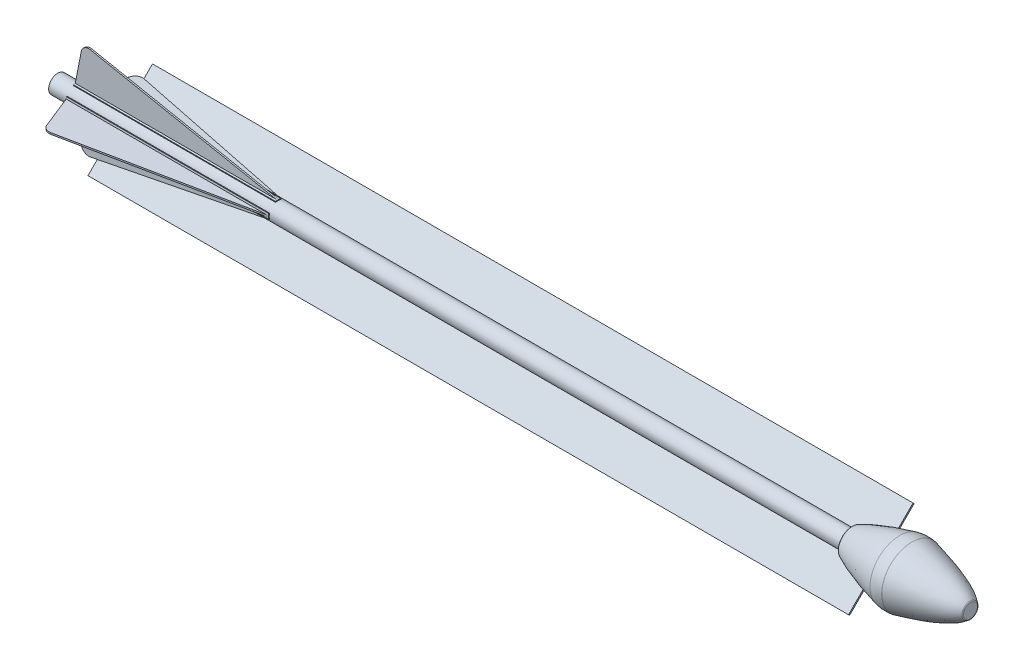
SolidWorks part; units mm, degrees
ref_plane "正面" through (0, 0, 0) normal (0, 0, 1) x (1, 0, 0)
ref_plane "平面" through (0, 0, 0) normal (0, 1, 0) x (1, 0, 0)
ref_plane "右側面" through (0, 0, 0) normal (1, 0, 0) x (0, 0, -1)
sketch "ｽｹｯﾁ1" plane through (0, 0, 0) normal (0, 0, 1) x (1, 0, 0)
  line L0 (-30.4177, 20.3227) -> (-30.4177, -19.1312)
  line L1 (-69.8771, 9.5958) -> (-69.8771, -8.4042)
  line L5 (8.174, 5.5958) -> (8.174, -4.4042)
  line L6 (-38.4177, 20.0342) -> (-38.4177, -18.8426)
  line L7 (10.8234, 0.5958) -> (-591.826, 0.5958)
  line L8 (-591.826, 6.5958) -> (-74.6461, 6.5958)
  line L9 (-591.826, 6.5958) -> (-591.826, -5.4042)
  line L10 (-591.826, -5.4042) -> (-74.6461, -5.4042)
  line L11 (-74.6461, 6.5958) -> (-74.6461, -5.4042)
  line L12 (-591.826, 6.5958) -> (-74.6461, -5.4042) construction
  line L13 (-591.826, -5.4042) -> (-74.6461, 6.5958) construction
  line L14 (-74.6461, -4.4042) -> (-591.826, -4.4042)
  line L15 (-74.6461, -4.4042) -> (-74.6461, 5.5958)
  line L16 (-74.6461, 5.5958) -> (-591.826, 5.5958)
  line L17 (-591.826, -4.4042) -> (-591.826, 5.5958)
  line L18 (-74.6461, -4.4042) -> (-591.826, 5.5958) construction
  line L19 (-74.6461, 5.5958) -> (-591.826, -4.4042) construction
  line L20 (-74.6461, 6.5958) -> (-56.932, 6.5958)
  line L21 (-74.6461, 6.5958) -> (-74.6461, -5.4042)
  line L22 (-74.6461, -5.4042) -> (-56.932, -5.4042)
  line L23 (-56.932, 6.5958) -> (-56.932, -5.4042)
  line L24 (-74.6461, 6.5958) -> (-56.932, -5.4042) construction
  line L25 (-74.6461, -5.4042) -> (-56.932, 6.5958) construction
  line L26 (-74.6461, 5.5958) -> (-56.932, 5.5958)
  line L27 (-74.6461, 5.5958) -> (-74.6461, -4.4042)
  line L28 (-74.6461, -4.4042) -> (-56.932, -4.4042)
  line L29 (-56.932, 5.5958) -> (-56.932, -4.4042)
  line L30 (-74.6461, 5.5958) -> (-56.932, -4.4042) construction
  line L31 (-74.6461, -4.4042) -> (-56.932, 5.5958) construction
  circle A0 centre (-33.7114, 0.5958) radius 20
  parabola Q1 (-38.4177, -18.8426) -> (-38.4177, 20.0342) focus (-76.1023, 0.5958) apex (-78.4613, 0.5958)
  parabola Q2 (-30.4177, -19.1312) -> (-30.4177, 20.3227) focus (8.4644, 0.5958) apex (10.8234, 0.5958)
  point P5 (-333.236, 0.5958)
  point P22 (-591.826, 0.5958)
  point P23 (-333.236, 0.5958)
  point P30 (-65.7891, 0.5958)
  point P33 (-65.7891, 0.5958)
  dimension "D1" = 40
  dimension "D18" = 40
  dimension "D7" = 20
  dimension "D9" = 0
  dimension "D10" = 0
  dimension "D11" = 20
  dimension "D13" = 20
  dimension "D15" = 20
  dimension "D2" = 18
  dimension "D5" = 10
  dimension "D8" = 2.359
  dimension "D19" = 78.0511
  dimension "D3" = 2.359
  dimension "D17" = 12
  dimension "D21" = 600
  dimension "D22" = 10
revolve "回転2" add sketch "ｽｹｯﾁ1" angle 360 about L7 region at (-23.4152, 8.6926, 0) region at (-34.4081, 10.5229, 0) region at (-44.7941, 8.4849, 0) region at (-57.1653, 10.2678, 0) region at (-6.3628, 7.5549, 0) region at (-63.4046, 6.0958, 0) region at (-72.2616, 6.0958, 0) region at (-333.5362, 6.0959, 0) region at (-75.0407, 5.934, 0)
fillet "ﾌｨﾚｯﾄ2" radius 1 2 edges at (-69.8771, 9.5958, 0) (8.174, 5.5958, 0)
sketch "ｽｹｯﾁ5" plane through (-591.826, 0, 0) normal (-1, 0, 0) x (0, 0, 1)
  circle A0 centre (0, 0.5958) radius 6.5
  circle A1 centre (0, 0.5958) radius 7.57
  dimension "D1" = 13
extrude "ﾎﾞｽ - 押し出し2" add sketch "ｽｹｯﾁ5" along normal blind 2 separate body
sketch "ｽｹｯﾁ6" plane through (0, 0, 0) normal (0, 0, 1) x (1, 0, 0)
  line L0 (-591.826, 6.5958) -> (-591.826, -5.4042) construction
  line L1 (-579.826, 2.2958) -> (-446.826, 2.2958)
  line L2 (-579.826, 2.2958) -> (-579.826, -1.1042)
  line L3 (-579.826, -1.1042) -> (-446.826, -1.1042)
  line L4 (-446.826, 2.2958) -> (-446.826, -1.1042)
  line L5 (-579.826, 2.2958) -> (-446.826, -1.1042) construction
  line L6 (-579.826, -1.1042) -> (-446.826, 2.2958) construction
  line L7 (-591.826, -5.4042) -> (-69.8771, -5.4042) construction
  point P4 (-513.326, 0.5958)
  point P7 (-579.826, 0.5958)
  dimension "D1" = 12
  dimension "D2" = 133
  dimension "D3" = 3.4
  dimension "D4" = 6
extrude "ﾎﾞｽ - 押し出し3" add sketch "ｽｹｯﾁ6" along normal up to surface and the other way up to surface up to face at (-593.826, -5.9042, 0) other way up to face at (-593.826, -5.9042, 0)
sketch "ｽｹｯﾁ7" plane through (0, 0, 0) normal (0, 1, 0) x (1, 0, 0)
  line L0 (-591.826, 6) -> (-591.826, -6) construction
  line L1 (-579.826, 1.7) -> (-446.826, 1.7)
  line L2 (-579.826, 1.7) -> (-579.826, -1.7)
  line L3 (-579.826, -1.7) -> (-446.826, -1.7)
  line L4 (-446.826, 1.7) -> (-446.826, -1.7)
  line L5 (-579.826, 1.7) -> (-446.826, -1.7) construction
  line L6 (-579.826, -1.7) -> (-446.826, 1.7) construction
  line L7 (-591.826, -6) -> (-579.826, -6) construction
  point P4 (-513.326, 0)
  point P7 (-579.826, 0)
  dimension "D1" = 3.4
  dimension "D2" = 133
  dimension "D3" = 12
  dimension "D4" = 6
extrude "ﾎﾞｽ - 押し出し4" add sketch "ｽｹｯﾁ7" along normal up to surface and the other way up to surface up to face at (-593.826, -5.9042, 0) other way up to face at (-593.826, -5.9042, 0)
sketch "ｽｹｯﾁ8" plane through (-593.826, 0, 0) normal (-1, 0, 0) x (0, 0, 1)
  circle A0 centre (0, 0.5958) radius 8.0163
  circle A1 centre (0, 0.5958) radius 5
  circle A2 centre (0, 0.5958) radius 6.5
  circle M3 centre (0, 0.5958) radius 7.57
  circle M4 centre (0, 0.5958) radius 6.5
extrude "ｶｯﾄ - 押し出し1" cut sketch "ｽｹｯﾁ8" against normal blind 182 and the other way blind 2 contours M3 M4 | A1 region at (-593.826, 0.5958, 0) region at (-593.826, 0.5958, -7.3558)
sketch "ｽｹｯﾁ9" plane through (-591.826, 0, 0) normal (-1, 0, 0) x (0, 0, 1)
  line L5 (0, 0.5958) -> (7, 0.5958)
  line L6 (0, 0.5958) -> (0, -6.4042)
  line L7 (0, -6.4042) -> (7, -6.4042)
  line L8 (7, 0.5958) -> (7, -6.4042)
  line L9 (0, 0.5958) -> (7, -6.4042) construction
  line L10 (0, -6.4042) -> (7, 0.5958) construction
  line L11 (0, 0.5958) -> (10, 0.5958)
  line L12 (0, 0.5958) -> (0, -9.4042)
  line L13 (0, -9.4042) -> (10, -9.4042)
  line L14 (10, 0.5958) -> (10, -9.4042)
  line L15 (0, 0.5958) -> (10, -9.4042) construction
  line L16 (0, -9.4042) -> (10, 0.5958) construction
  point P4 (3.5, -2.9042)
  point P10 (5, -4.4042)
  dimension "D1" = 7
  dimension "D2" = 7
  dimension "D3" = 10
  dimension "D4" = 10
extrude "ﾎﾞｽ - 押し出し5" add sketch "ｽｹｯﾁ9" along normal blind 12 separate body contours L14 L11 L8 L7 L12 L13 region at (-591.826, 0.4543, 8.5)
sketch "ｽｹｯﾁ10" plane through (0, 0.5958, 0) normal (0, 1, 0) x (1, 0, 0)
  line L0 (-579.826, 1.7) -> (-579.826, -1.7) construction
  line L1 (-579.826, -31.5) -> (-447.826, -31.5)
  line L2 (-579.826, -31.5) -> (-579.826, -5.5)
  line L3 (-579.826, -5.5) -> (-447.826, -5.5)
  line L4 (-447.826, -31.5) -> (-447.826, -5.5)
  line L5 (-579.826, -31.5) -> (-447.826, -5.5) construction
  line L6 (-579.826, -5.5) -> (-447.826, -31.5) construction
  line L7 (-579.826, -6.5) -> (-446.826, -6.5) construction
  line L8 (-579.826, -6.5) -> (-569.826, -31.5)
  line L9 (-569.826, -31.5) -> (-447.826, -6.5)
  line L10 (-608.1921, 0) -> (-614.5212, 0) construction
  line L11 (-579.826, 5.5) -> (-447.826, 31.5) construction
  line L12 (-579.826, 31.5) -> (-447.826, 5.5) construction
  line L13 (-569.826, 31.5) -> (-447.826, 6.5)
  line L14 (-579.826, 6.5) -> (-569.826, 31.5)
  line L15 (-447.826, 31.5) -> (-447.826, 5.5)
  line L16 (-579.826, 5.5) -> (-447.826, 5.5)
  line L17 (-579.826, 31.5) -> (-579.826, 5.5)
  line L18 (-579.826, 31.5) -> (-447.826, 31.5)
  circle A0 centre (-566.7357, -25.7628) radius 5
  circle A1 centre (-566.7357, 25.7628) radius 5
  point P4 (-513.826, -18.5)
  point P26 (-513.826, 18.5)
  dimension "D5" = 10
  dimension "D1" = 26
  dimension "D2" = 0
  dimension "D3" = 1
  dimension "D4" = 132
  dimension "D6" = 10
extrude "ﾎﾞｽ - 押し出し6" add sketch "ｽｹｯﾁ10" along normal blind 0.5 and the other way blind 0.5 contours L13 A1 L14 L17 L16 L15 | A1 | A0 L9 L4 L3 L2 L8 | A0 region at (-529.3857, 0.5958, 13.6104) region at (-566.7357, 0.5958, 25.7628) region at (-529.3857, 0.5958, -13.6104) region at (-566.7357, 0.5958, -25.7628)
sketch "ｽｹｯﾁ11" plane through (0, 0, 0) normal (0, 0, -1) x (-1, 0, 0)
  line L0 (579.826, 7.0958) -> (446.826, 7.0958) construction
  line L1 (579.826, 6.0958) -> (447.826, 6.0958)
  line L2 (579.826, 6.0958) -> (579.826, 32.0958)
  line L3 (579.826, 32.0958) -> (447.826, 32.0958)
  line L4 (447.826, 6.0958) -> (447.826, 32.0958)
  line L5 (579.826, 6.0958) -> (447.826, 32.0958) construction
  line L6 (579.826, 32.0958) -> (447.826, 6.0958) construction
  line L7 (579.826, 6.8695) -> (579.826, 6.3499) construction
  line L8 (579.826, 7.0958) -> (574.9079, 32.0958)
  line L9 (574.9079, 32.0958) -> (447.826, 7.0958)
  line L14 (603.826, 0.5958) -> (610.125, 0.5958) construction
  line L15 (579.826, -30.9042) -> (447.826, -4.9042) construction
  line L16 (579.826, -4.9042) -> (447.826, -30.9042) construction
  line L17 (574.9079, -30.9042) -> (447.826, -5.9042)
  line L18 (579.826, -5.9042) -> (574.9079, -30.9042)
  line L19 (447.826, -4.9042) -> (447.826, -30.9042)
  line L20 (579.826, -30.9042) -> (447.826, -30.9042)
  line L21 (579.826, -4.9042) -> (579.826, -30.9042)
  line L22 (579.826, -4.9042) -> (447.826, -4.9042)
  circle A0 centre (570.9671, 26.2247) radius 5
  circle A1 centre (570.9671, -25.0332) radius 5
  point P4 (513.826, 19.0958)
  point P26 (513.826, -17.9042)
  dimension "D7" = 10
  dimension "D1" = 26
  dimension "D2" = 1
  dimension "D3" = 132
  dimension "D4" = 0
  dimension "D5" = 0
  dimension "D6" = 0
extrude "ﾎﾞｽ - 押し出し7" add sketch "ｽｹｯﾁ11" along normal blind 0.5 and the other way blind 0.5 contours L17 A1 L18 L21 L22 L19 | A0 L9 L4 L1 L2 L8 | A0 | A1 region at (-530.7769, 14.1946, 0) region at (-570.9671, 26.2247, 0) region at (-530.7769, -13.0031, 0)
sketch "ｽｹｯﾁ12" plane through (0, 0, 0) normal (0, 0, -1) x (-1, 0, 0)
  line L1 (591.826, -9.4042) -> (609.9524, -9.4042)
  line L2 (591.826, -9.4042) -> (591.826, 7.468)
  line L3 (591.826, 7.468) -> (609.9524, 7.468)
  line L4 (609.9524, -9.4042) -> (609.9524, 7.468)
  line L5 (591.826, -9.4042) -> (609.9524, 7.468) construction
  line L6 (591.826, 7.468) -> (609.9524, -9.4042) construction
  point P4 (600.8892, -0.9681)
extrude "ｶｯﾄ - 押し出し2" cut sketch "ｽｹｯﾁ12" against normal blind 30.5
fillet "ﾌｨﾚｯﾄ3" radius 1 1 edges at (-30.4177, 20.3227, 0)
ref_plane "平面1" through (-571.3781, 0, 0) normal (1, 0, 0) x (0, 0, -1)
sketch "ｽｹｯﾁ14" plane through (-571.3781, 0, 0) normal (1, 0, 0) x (0, 0, -1)
  line L2 (28.2843, 0.5958) -> (0, -27.6885) construction
  line L4 (0.1041, -41.9347) -> (42.5305, 0.4917)
  line L5 (14.1421, -13.5464) -> (20.6102, -20.0144) construction
  line L10 (0.1041, -41.9347) -> (-0.603, -41.2276)
  line L11 (-0.603, -41.2276) -> (41.8234, 1.1988)
  line L12 (41.8234, 1.1988) -> (42.5305, 0.4917)
  line L13 (6.5, 0.0958) -> (27.6198, 0.0958) construction
  circle A0 centre (0, 0.5958) radius 6 construction
  circle A1 centre (0, 0.5958) radius 5 construction
  point P1 (0.316, -25.8831)
  point P9 (27.5424, 0)
  point P10 (0, 0)
  dimension "D6" = 0
  dimension "D1" = 20
  dimension "D2" = 45
  dimension "D3" = 40
  dimension "D4" = 60
  dimension "D5" = 1
  dimension "D7" = 9.1472
extrude "ﾎﾞｽ - 押し出し8" add sketch "ｽｹｯﾁ14" along normal blind 500
equation "\"a\"=2.359"
equation "\"D8@ｽｹｯﾁ1\"=\"a\""
equation "\"D3@ｽｹｯﾁ1\"=\"a\""
